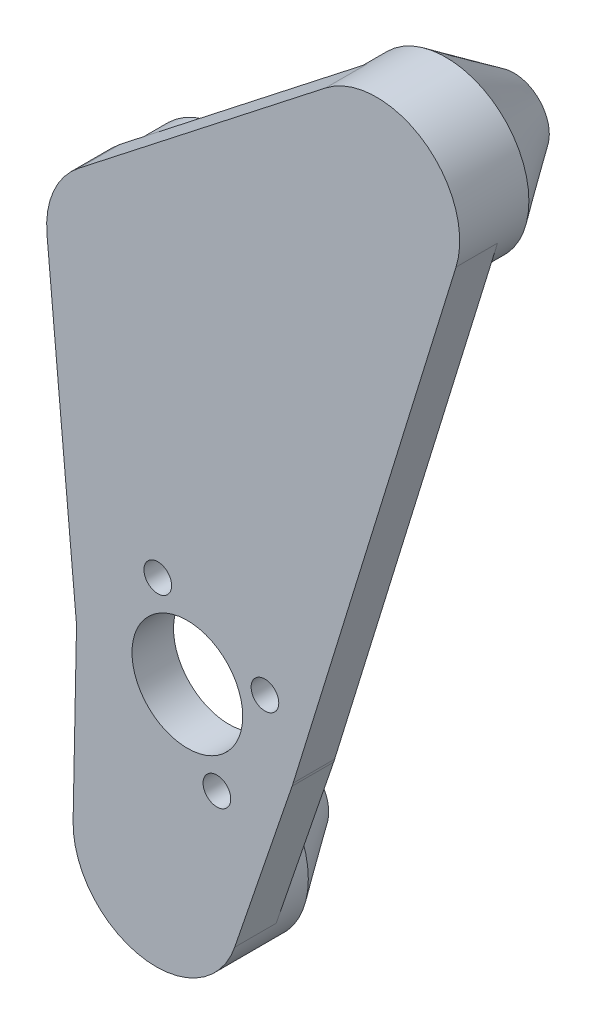
SolidWorks part; units mm, degrees
note: '?' marks a value the reader was unsure of. The reader was unsure of these and kept them because the rebuilt part matched: shared geometry of "Sketch1<4>", "Sketch2<4>".
ref_plane "Front Plane" through (0, 0, 0) normal (0, 0, 1) x (1, 0, 0)
ref_plane "Top Plane" through (0, 0, 0) normal (0, 1, 0) x (1, 0, 0)
ref_plane "Right Plane" through (0, 0, 0) normal (1, 0, 0) x (0, 0, -1)
sketch "Sketch1" plane through (0, 0, 0) normal (0, 0, 1) x (1, 0, 0)
  line L0 (0, 0) -> (-64.9837, 0) construction
  line L1 (0, 0) -> (-4.1676, 23.6354) construction
  line L2 (0, 0) -> (13.6808, 37.5877) construction
  line L3 (-10.1427, 23.0895) -> (-7.9668, -0.7278)
  line L4 (-7.8628, 28.3625) -> (9.9856, 42.3148)
  line L5 (19.4145, 35.8201) -> (7.6449, -2.3569)
  circle A0 centre (0, 0) radius 8
  arc A1 (-7.8628, 28.3625) -> (-10.1427, 23.0895) centre (-4.1676, 23.6354) ccw
  circle A2 centre (13.6808, 37.5877) radius 6
  circle A4 centre (13.6808, 37.5877) radius 4 construction
  circle A5 centre (-2.1676, 25.1988) radius 6
  circle A6 centre (-2.1676, 25.1988) radius 4 construction
  dimension "D1" = 16
  dimension "D4" = 12
  dimension "D7" = 12
  dimension "D8" = 12
  dimension "D9" = 8
  dimension "D10" = 2
  dimension "D2" = 24
  dimension "D3" = 80
  dimension "D5" = 40
  dimension "D6" = 110
sketch "Sketch2" plane through (0, 0, 0) normal (0, 0, 1) x (1, 0, 0)
  line L0 (0, 0) -> (-64.9837, 0) construction
  line L1 (-8.2562, -12.6821) -> (-7.9984, 0.1606)
  line L2 (0, 0) -> (-2.2574, -12.8025) construction
  line L3 (3.4208, -14.741) -> (7.5709, -2.5847)
  circle A0 centre (0, 0) radius 8
  circle A2 centre (-2.2574, -12.8025) radius 6
  circle A4 centre (-2.2574, -12.8025) radius 4 construction
  dimension "D5" = 80
  dimension "D6" = 12
  dimension "D7" = 8
  dimension "D4" = 13
extrude "Boss-Extrude1" add sketch "Sketch1" along normal blind 3 contours A2 L4 A1 L3 A0 L5 | A1 | A2 | A0 | A5
extrude "Boss-Extrude2" add sketch "Sketch2" along normal blind 3
sketch "Sketch3" plane through (0, 0, 3) normal (0, 0, 1) x (1, 0, 0)
  circle A0 centre (0, 0) radius 4
  dimension "D1" = 8
extrude "Cut-Extrude1" cut sketch "Sketch3" against normal blind 50
ref_axis "Axis1" through (13.6808, 37.5877, 0) along (0, 0, 1)?
ref_axis "Axis2" through (-2.1676, 25.1988, 0) along (0, 0, 1)?
ref_axis "Axis3" through (-2.2574, -12.8025, 0) along (0, 0, 1)?
ref_axis "Axis4" through (0, 0, 0) along (0, 0, 1)?
sketch "Sketch4" plane through (0, 0, 3) normal (0, 0, 1) x (1, 0, 0)
  line L0 (0, 0) -> (2.1355, -5.6071)
  line L1 (0, 0) -> (-64.9837, 0) construction
  circle A0 centre (2.1355, -5.6071) radius 1
  circle A7 centre (-5.6071, -2.1355) radius 1
  circle A8 centre (-2.1355, 5.6071) radius 1
  circle A9 centre (5.6071, 2.1355) radius 1
  point P15 (0, 0)
  point P16 (0, 0)
  point P17 (0, 0)
  dimension "D3" = 2
  dimension "D1" = 110.85
  dimension "D2" = 6
  dimension "D4" = 4
extrude "Cut-Extrude2" cut sketch "Sketch4" against normal blind 10 contours A0 | A8 | A9
extrude "Boss-Extrude3" add sketch "Sketch1<4>" against normal blind 7 contours A2 | A5
sketch "Sketch1<4>" plane through (0, 0, 0) normal (0, 0, 1) x (1, 0, 0) same geometry as "Sketch1"
extrude "Boss-Extrude4" add sketch "Sketch2<4>" against normal blind 7 contours A2
sketch "Sketch2<4>" plane through (0, 0, 0) normal (0, 0, 1) x (1, 0, 0) same geometry as "Sketch2"
ref_point "Point2"
ref_point "Point4"
ref_point "Point6"
ref_plane "Plane1" through (13.6808, 0, 0) normal (1, 0, 0) x (0, 0, -1)
ref_plane "Plane2" through (-2.1676, 0, 0) normal (1, 0, 0) x (0, 0, -1)
ref_plane "Plane3" through (-2.2574, 0, 0) normal (1, 0, 0) x (0, 0, -1)
sketch "Sketch5" plane through (13.6808, 0, 0) normal (1, 0, 0) x (0, 0, -1)
  line L0 (7, 37.5877) -> (10, 37.5877) construction
  line L1 (0, 37.5877) -> (-22.8237, 37.5877) construction
  line L2 (10, 41.5877) -> (10, 33.5877)
  circle A0 centre (10, 37.5877) radius 4
  dimension "D2" = 8
  dimension "D1" = 3
sketch "Sketch6" plane through (-2.1676, 0, 0) normal (1, 0, 0) x (0, 0, -1)
  line L0 (7, 25.1988) -> (10, 25.1988) construction
  line L1 (0, 25.1988) -> (-22.8237, 25.1988) construction
  line L2 (10, 29.1988) -> (10, 21.1988)
  circle A0 centre (10, 25.1988) radius 4
  dimension "D2" = 8
  dimension "D1" = 3
sketch "Sketch7" plane through (-2.2574, 0, 0) normal (1, 0, 0) x (0, 0, -1)
  line L0 (7, -12.8025) -> (10, -12.8025) construction
  line L1 (10, -8.8025) -> (10, -16.8025)
  circle A0 centre (10, -12.8025) radius 4
  dimension "D2" = 8
  dimension "D1" = 3
revolve "Cut-Revolve1" cut sketch "Sketch5" angle 360 about L2
revolve "Cut-Revolve2" cut sketch "Sketch6" angle 360 about L2
revolve "Cut-Revolve3" cut sketch "Sketch7" angle 360 about L1
chamfer "Chamfer1" distance 5 angle 35 3 edges at (3.7426, -12.8025, -7) (19.6808, 37.5877, -7) (3.8324, 25.1988, -7)
